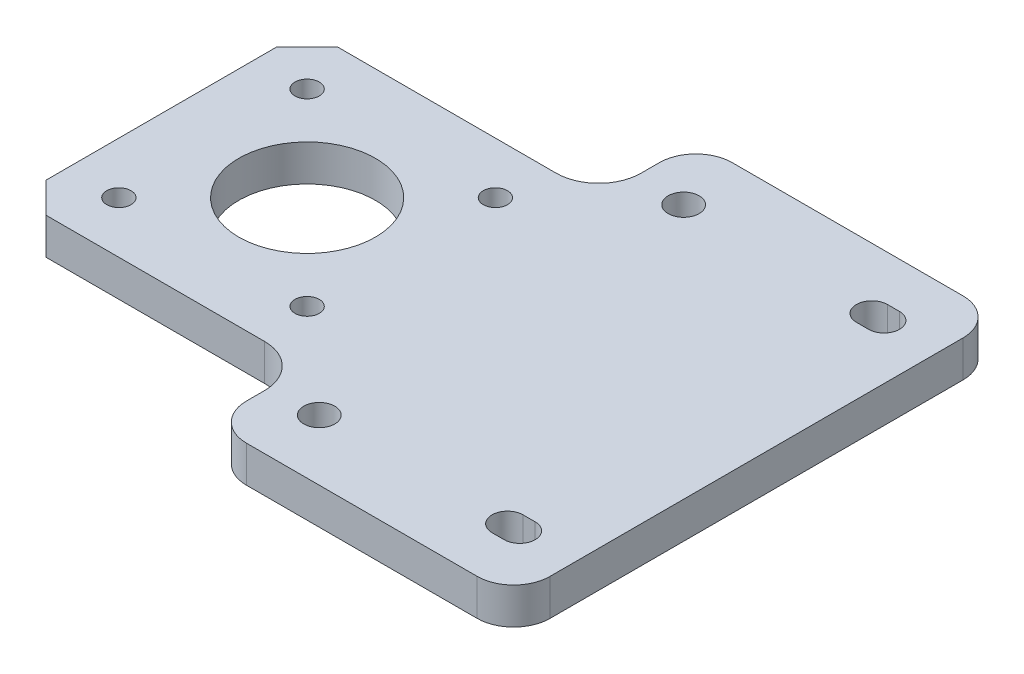
SolidWorks part; units mm, degrees
material "Клен"
ref_plane "Спереди" through (0, 0, 0) normal (0, 0, 1) x (1, 0, 0)
ref_plane "Сверху" through (0, 0, 0) normal (0, 1, 0) x (1, 0, 0)
ref_plane "Справа" through (0, 0, 0) normal (1, 0, 0) x (0, 0, -1)
sketch "Эскиз1" plane through (0, 0, 0) normal (0, 1, 0) x (1, 0, 0)
  line L0 (-56.8562, 0) -> (56.8562, 0) construction
  line L9 (-32, -24) -> (-68, -24)
  line L10 (-19, -40) -> (19, -40)
  line L11 (-25, -34) -> (-25, -31)
  line L12 (-19, 40) -> (19, 40)
  line L13 (25, -34) -> (25, 34)
  line L14 (-25, -40) -> (25, 40) construction
  line L15 (-25, 40) -> (25, -40) construction
  line L20 (-73, -19) -> (-73, 19)
  line L21 (-32, 24) -> (-68, 24)
  line L22 (-25, 31) -> (-25, 34)
  line L23 (-68, -24) -> (-73, -19)
  line L24 (-68, 24) -> (-73, 19)
  line L25 (-73, -24) -> (-25, 24) construction
  line L26 (-25, -24) -> (-72.5248, 23.5248) construction
  line L27 (-49, -29.3961) -> (-49, 34.1878) construction
  arc A4 (19, 40) -> (25, 34) centre (19, 34) cw
  arc A5 (19, -40) -> (25, -34) centre (19, -34) ccw
  arc A6 (-19, -40) -> (-25, -34) centre (-19, -34) cw
  arc A7 (-25, 34) -> (-19, 40) centre (-19, 34) cw
  circle A8 centre (-49, 0) radius 11.25
  circle A9 centre (-64.5, 15.5) radius 2
  circle A10 centre (-64.5, -15.5) radius 2
  circle A11 centre (-33.5, 15.5) radius 2
  circle A12 centre (-33.5, -15.5) radius 2
  arc A13 (-25, -31) -> (-32, -24) centre (-32, -31) ccw
  arc A14 (-32, 24) -> (-25, 31) centre (-32, 31) ccw
  point P0 (0, 0)
  point P22 (-73, -24)
  point P24 (-73, 24)
  point P25 (-75, 0)
  point P32 (-49, 0)
  point P34 (-49.8171, 0.0009)
  point P35 (-49, 0)
  point P36 (-24.7404, 0.0009)
  point P37 (-49, 0)
  point P39 (-49, 0)
  point P56 (-25, 32.5)
  dimension "D1" = 6
  dimension "D6" = 22.5
  dimension "D7" = 4
  dimension "D13" = 7
  dimension "D14" = 7
  dimension "D2" = 80
  dimension "D3" = 50
  dimension "D4" = 48
  dimension "D10" = 15.5
  dimension "D11" = 15.5
  dimension "D12" = 15.5
  dimension "D5" = 48
extrude "Бобышка-Вытянуть1" add sketch "Эскиз1" along normal blind 6
sketch "Эскиз2" plane through (0, 0, 0) normal (0, -1, 0) x (1, 0, 0)
  line L0 (0, -37.0349) -> (0, 29.2907) construction
  line L1 (16, -30) -> (14, -30) construction
  line L2 (16, -32.55) -> (14, -32.55)
  line L3 (16, -27.45) -> (14, -27.45)
  line L6 (-46.1924, 0) -> (55.6646, 0) construction
  line L7 (16, 30) -> (14, 30) construction
  line L8 (16, 32.55) -> (14, 32.55)
  line L9 (16, 27.45) -> (14, 27.45)
  line L10 (-25, 31) -> (-25, 34) construction
  line L11 (19, -40) -> (-19, -40) construction
  circle A0 centre (-17, -30) radius 2.55
  arc A1 (16, -32.55) -> (16, -27.45) centre (16, -30) ccw
  arc A2 (14, -27.45) -> (14, -32.55) centre (14, -30) ccw
  arc A3 (16, 32.55) -> (16, 27.45) centre (16, 30) cw
  arc A4 (14, 27.45) -> (14, 32.55) centre (14, 30) cw
  circle A5 centre (-17, 30) radius 2.55
  point P7 (15, -30)
  point P12 (15, -32.55)
  point P21 (15, 30)
  dimension "D1" = 5.1
  dimension "D2" = 5.1
  dimension "D4" = 33
  dimension "D5" = 8
  dimension "D6" = 10
extrude "Вырез-Вытянуть1" cut sketch "Эскиз2" against normal through all
equation "\"D2@Эскиз2\"=\"D1@Эскиз2\""
equation "\"D5@Эскиз1\"=\"D4@Эскиз1\""
